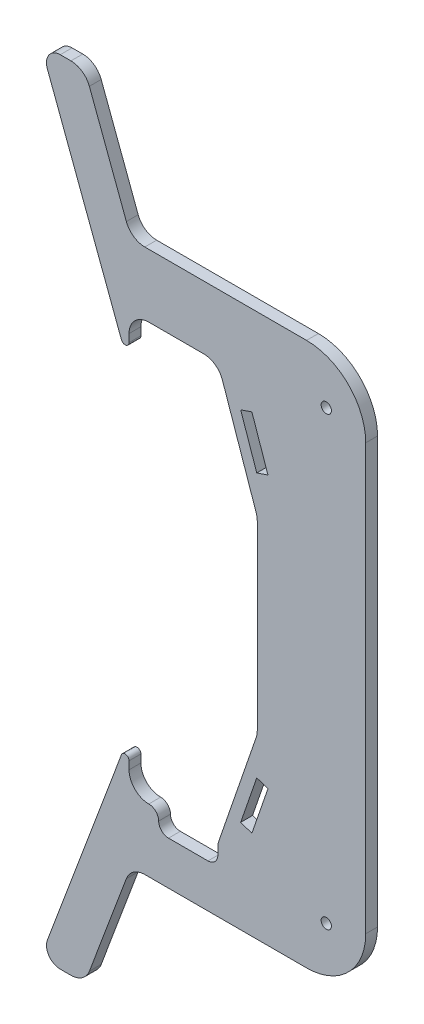
SolidWorks part; units mm, degrees
material "MDF"
ref_plane "Plano frontal" through (0, 0, 0) normal (0, 0, 1) x (1, 0, 0)
ref_plane "Plano superior" through (0, 0, 0) normal (0, 1, 0) x (1, 0, 0)
ref_plane "Plano direito" through (0, 0, 0) normal (1, 0, 0) x (0, 0, -1)
sketch "Esboço1" plane through (0, 0, 0) normal (0, 0, 1) x (1, 0, 0)
  line L0 (-20, 127.8) -> (-100, 127.8)
  line L1 (-20, -127.8) -> (20, -127.8)
  line L2 (-20, -127.8) -> (-20, 127.8)
  line L3 (-20, 127.8) -> (20, 127.8)
  line L4 (20, -127.8) -> (20, 127.8)
  line L5 (-20, -127.8) -> (20, 127.8) construction
  line L6 (-20, 127.8) -> (20, -127.8) construction
  line L7 (0, 0) -> (20, 0) construction
  line L8 (-145, 200.8) -> (-100, 80.8)
  line L9 (-100, 80.8) -> (-20, 80.8)
  line L10 (-100, 127.8) -> (-100, 200.8)
  line L11 (-145, -200.8) -> (-100, -80.8)
  line L12 (-100, -80.8) -> (-20, -80.8)
  line L13 (-100, 80.8) -> (-100, 105.8)
  line L14 (-100, 105.8) -> (-20, 105.8)
  line L15 (-20, 105.8) -> (-20, 80.8)
  line L16 (-20, -105.8) -> (-20, -80.8)
  line L17 (-100, -80.8) -> (-100, -105.8)
  line L18 (-100, -105.8) -> (-20, -105.8)
  line L19 (-100, 200.8) -> (-145, 200.8)
  line L20 (-100, -200.8) -> (-145, -200.8)
  line L21 (-20, -127.8) -> (-100, -127.8)
  line L22 (-100, -127.8) -> (-100, -200.8)
  line L23 (-100, 140.6203) -> (-95.1924, 127.8)
  line L24 (-100, -140.6203) -> (-95.1924, -127.8)
  line L25 (-100, 140.6203) -> (-122.5674, 200.8)
  line L26 (-100, -140.6203) -> (-122.5674, -200.8)
  line L27 (-55, 105.8) -> (-35, 47.8)
  line L28 (-55, -105.8) -> (-35, -47.8)
  line L29 (-35, 47.8) -> (-35, -47.8)
  line L30 (-37.7304, -92.5291) -> (-43.4026, -90.5731)
  line L31 (-55, -115.8) -> (-85, -115.8)
  line L32 (-55, -115.8) -> (-55, -105.8)
  line L33 (-55, -105.8) -> (-85, -105.8)
  line L34 (-85, -115.8) -> (-85, -105.8)
  line L35 (-70, -105.8) -> (-70, -115.8) construction
  line L36 (-55, -110.8) -> (-85, -110.8) construction
  line L37 (-43.4026, -90.5731) -> (-35.2529, -66.9388)
  line L38 (-35.2529, -66.9388) -> (-29.5806, -68.8947)
  line L39 (-29.5806, -68.8947) -> (-37.7304, -92.5291)
  line L40 (-45, -76.8) -> (-39.3278, -78.7559) construction
  line L41 (-35.2529, 66.9388) -> (-29.5806, 68.8947)
  line L42 (-43.4026, 90.5731) -> (-35.2529, 66.9388)
  line L43 (-37.7304, 92.5291) -> (-43.4026, 90.5731)
  line L44 (-29.5806, 68.8947) -> (-37.7304, 92.5291)
  line L45 (-98.9424, 137.8) -> (20, 137.8)
  line L46 (20, 137.8) -> (20, 127.8)
  line L47 (20, -137.8) -> (20, -127.8)
  line L48 (-98.9424, -137.8) -> (20, -137.8)
  circle A1 centre (0, 113.2) radius 2.6
  circle A2 centre (0, -113.2) radius 2.6
  point P0 (0, 0)
  point P34 (0, 127.8)
  point P38 (-70, -110.8)
  dimension "D2" = 14.6
  dimension "D3" = 5.2
  dimension "D1" = 255.6
  dimension "D4" = 40
  dimension "D5" = 125
  dimension "D6" = 80
  dimension "D7" = 80
  dimension "D8" = 120
  dimension "D9" = 47
  dimension "D10" = 25
  dimension "D11" = 21.0043
  dimension "D12" = 12
  dimension "D13" = 80
  dimension "D14" = 75
  dimension "D15" = 15
  dimension "D16" = 75
  dimension "D17" = 30
  dimension "D18" = 6
  dimension "D19" = 6
  dimension "D20" = 25
  dimension "D21" = 10
extrude "Ressalto-extrusão1" add sketch "Esboço1" along normal blind 6 contours L1 L4 L3 L2 A1 A2 | L22 L24 L21 | L23 L10 L0 | L28 L18 L2 L12 | L28 L12 L2 | L10 L25 L19 L8 L13 L14 L2 L0 | L14 L27 L9 L2 | L26 L22 L21 L2 L18 L17 L11 L20 | L46 L45 L23 L0 L3 | L24 L48 L47 L1 L21 region at (-21.7328, 116.8, 0) region at (0, 0, 0) region at (-38.5387, 132.8267, 0) region at (-98.3975, 132.0734, 0) region at (-35.1357, 94.6363, 0) region at (-28.6612, 0, 0) region at (-38.5387, -132.8267, 0) region at (-35.1357, -94.6363, 0) region at (-57.5962, -126.0672, 0) region at (-98.3975, -132.0734, 0)
fillet "Filete1" radius 2 2 edges at (-100, -80.8, 3) (-100, 80.8, 3)
fillet "Filete3" radius 10 10 edges at (-122.5674, -200.8, 3) (-100, -105.8, 3) (-100, 105.8, 3) (-122.5674, 200.8, 3) (-55, 105.8, 3) (-35, -47.8, 3) (-35, 47.8, 3) (-55, -105.8, 3) (-98.9424, 137.8, 3) (-98.9424, -137.8, 3)
fillet "Filete4" radius 7 2 edges at (-145, 200.8, 3) (-145, -200.8, 3)
fillet "Filete5" radius 5 3 edges at (-85, -115.8, 3) (-55, -115.8, 3) (-85, -105.8, 3)
fillet "Filete6" radius 30 2 edges at (20, -137.8, 3) (20, 137.8, 3)
